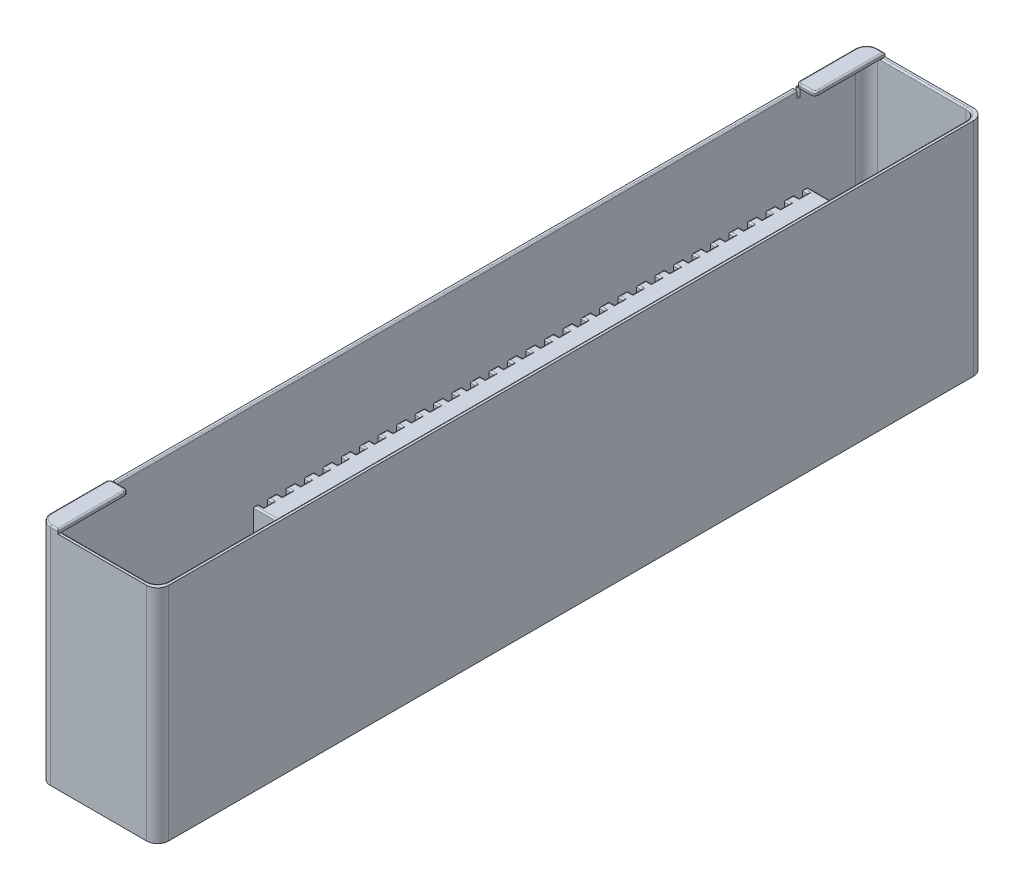
SolidWorks part; units mm, degrees
ref_plane "Front Plane" through (0, 0, 0) normal (0, 0, 1) x (1, 0, 0)
ref_plane "Top Plane" through (0, 0, 0) normal (0, 1, 0) x (1, 0, 0)
ref_plane "Right Plane" through (0, 0, 0) normal (1, 0, 0) x (0, 0, -1)
sketch "Sketch1" plane through (0, 0, 0) normal (0, 1, 0) x (1, 0, 0)
  line L0 (0, 0) -> (0, 2.2917) construction
  line L1 (-1.6, 11.2) -> (1.6, 11.2)
  line L2 (-1.6, 11.2) -> (-1.6, -11.2)
  line L3 (-1.6, -11.2) -> (1.6, -11.2)
  line L4 (1.6, 11.2) -> (1.6, -11.2)
  line L5 (0, 0) -> (0.8, 0) construction
  line L6 (-1.5, 11.1) -> (1.5, 11.1)
  line L7 (1.5, 11.1) -> (1.5, -11.1)
  line L8 (-1.5, -11.1) -> (1.5, -11.1)
  line L9 (-1.5, 11.1) -> (-1.5, -11.1)
  line L10 (-0.1, -0.1) -> (0.8, -0.1)
  line L11 (-0.1, -0.1) -> (-0.1, 2.2917)
  dimension "D1" = 3.2
  dimension "D2" = 22.4
  dimension "D3" = 0.1
extrude "Boss-Extrude1" add sketch "Sketch1" along normal blind 6 contours L4 L1 L2 L3 L9 L6 L7 L8
sketch "Sketch2" plane through (0, 0, 0) normal (0, -1, 0) x (1, 0, 0)
  line L1 (-1.6, 11.2) -> (1.6, 11.2)
  line L2 (-1.6, 11.2) -> (-1.6, -11.2)
  line L3 (-1.6, -11.2) -> (1.6, -11.2)
  line L4 (1.6, 11.2) -> (1.6, -11.2)
extrude "Boss-Extrude2" add sketch "Sketch2" against normal blind 0.1
sketch "Sketch3" plane through (0, 6, 0) normal (0, 1, 0) x (1, 0, 0)
  line L0 (-1.5, -11.1) -> (-1.5, -9.3) construction
  line L1 (-1.5, -11.1) -> (-1.5, 11.1) construction
  line L2 (-1.5, -9.3) -> (-1.2, -9.3)
  line L3 (-1.6, 11.2) -> (-1.6, -11.2) construction
  line L4 (-1.1, -9.4) -> (-1.1, -11.1)
  line L5 (-1.5, -11.1) -> (1.5, -11.1) construction
  line L6 (-1.1, -11.1) -> (-1.1, -11.2)
  line L7 (-1.6, -11.1) -> (-1.6, -9.4)
  line L8 (-1.6, -11.2) -> (1.6, -11.2) construction
  line L9 (-1.1, -11.2) -> (-1.6, -11.2)
  line L10 (-1.6, -11.2) -> (-1.6, -11.1)
  arc A0 (-1.5, -9.3) -> (-1.6, -9.4) centre (-1.5, -9.4) ccw
  arc A1 (-1.2, -9.3) -> (-1.1, -9.4) centre (-1.2, -9.4) cw
  point P15 (-1.6, -9.3)
  dimension "D3" = 0.1
  dimension "D1" = 1.8
  dimension "D2" = 0.5
extrude "Boss-Extrude4" add sketch "Sketch3" along normal blind 0.1
mirror "Mirror1" about plane through (0, 0, 0) normal (0, 0, 1) of "Boss-Extrude4"
sketch "Sketch4" plane through (0, 6, 0) normal (0, 1, 0) x (1, 0, 0)
  line L0 (-1.5, 9.3) -> (-1.2, 9.3)
  line L1 (-1.2, 9.3) -> (-1.2, 9.2142)
  line L2 (-1.2, 9.2142) -> (-1.7728, 9.2142)
  line L3 (-1.7728, 9.2142) -> (-1.7728, 9.3)
  line L4 (-1.7728, 9.3) -> (-1.5, 9.3)
  line L5 (0, 0) -> (-2.7647, 0) construction
  line L6 (-1.2, -9.3) -> (-1.2, -9.2142)
  line L7 (-1.7728, -9.2142) -> (-1.7728, -9.3)
  line L8 (-1.7728, -9.3) -> (-1.5, -9.3)
  line L9 (-1.5, -9.3) -> (-1.2, -9.3)
  line L10 (-1.2, -9.2142) -> (-1.7728, -9.2142)
extrude "Cut-Extrude1" cut sketch "Sketch4" against normal blind 0.2
sketch "Sketch5" plane through (0, 0.1, 0) normal (0, 1, 0) x (1, 0, 0)
  line L0 (0, 0) -> (1.3, 0) construction
  line L1 (1.3, 0) -> (1.3, 7.5)
  line L2 (1.3, 0) -> (1.3, -7.5)
  line L3 (1.5, 0) -> (1.3, 0) construction
  line L4 (1.5, 11.1) -> (1.5, -11.1) construction
  line L5 (1.3, 7.5) -> (0.5, 7.5)
  line L6 (0.5, 7.5) -> (0.5, -7.5)
  line L7 (0.5, -7.5) -> (1.3, -7.5)
  line L10 (0.5, 0.125) -> (0.5, -0.125)
  dimension "D1" = 0.2
  dimension "D2" = 7.5
  dimension "D3" = 7.5
  dimension "D4" = 0.8
extrude "Boss-Extrude5" add sketch "Sketch5" along normal blind 5.5 contours L6 L7 L2 L1 L5
sketch "Sketch6" plane through (0, 5.6, 0) normal (0, 1, 0) x (1, 0, 0)
  line L0 (0.5, 0) -> (0.7046, 0) construction
  line L1 (0.5, 7.5) -> (0.5, -7.5) construction
  line L2 (0.5, 0) -> (0.5, -0.125) construction
  line L3 (0.5, 7.5) -> (0.5, -7.5) construction
  line L4 (0.5, 0) -> (0.5, 0.125) construction
  line L5 (0.5, 0.125) -> (0.65, 0.125)
  line L6 (0.65, 0.125) -> (0.65, 0.375)
  line L7 (0.65, 0.375) -> (0.5, 0.375)
  line L8 (0.5, 0.375) -> (0.5, 0.125)
  line L9 (0.65, 0.875) -> (0.5, 0.875)
  line L10 (0.65, 0.625) -> (0.65, 0.875)
  line L11 (0.5, 0.625) -> (0.65, 0.625)
  line L12 (0.5, 0.875) -> (0.5, 0.625)
  line L13 (0.65, 1.375) -> (0.5, 1.375)
  line L14 (0.65, 1.125) -> (0.65, 1.375)
  line L15 (0.5, 1.125) -> (0.65, 1.125)
  line L16 (0.5, 1.375) -> (0.5, 1.125)
  line L17 (0.65, 1.875) -> (0.5, 1.875)
  line L18 (0.65, 1.625) -> (0.65, 1.875)
  line L19 (0.5, 1.625) -> (0.65, 1.625)
  line L20 (0.5, 1.875) -> (0.5, 1.625)
  line L21 (0.65, 2.375) -> (0.5, 2.375)
  line L22 (0.65, 2.125) -> (0.65, 2.375)
  line L23 (0.5, 2.125) -> (0.65, 2.125)
  line L24 (0.5, 2.375) -> (0.5, 2.125)
  line L25 (0.65, 2.875) -> (0.5, 2.875)
  line L26 (0.65, 2.625) -> (0.65, 2.875)
  line L27 (0.5, 2.625) -> (0.65, 2.625)
  line L28 (0.5, 2.875) -> (0.5, 2.625)
  line L29 (0.65, 3.375) -> (0.5, 3.375)
  line L30 (0.65, 3.125) -> (0.65, 3.375)
  line L31 (0.5, 3.125) -> (0.65, 3.125)
  line L32 (0.5, 3.375) -> (0.5, 3.125)
  line L33 (0.65, 3.875) -> (0.5, 3.875)
  line L34 (0.65, 3.625) -> (0.65, 3.875)
  line L35 (0.5, 3.625) -> (0.65, 3.625)
  line L36 (0.5, 3.875) -> (0.5, 3.625)
  line L37 (0.65, 4.375) -> (0.5, 4.375)
  line L38 (0.65, 4.125) -> (0.65, 4.375)
  line L39 (0.5, 4.125) -> (0.65, 4.125)
  line L40 (0.5, 4.375) -> (0.5, 4.125)
  line L41 (0.65, 4.875) -> (0.5, 4.875)
  line L42 (0.65, 4.625) -> (0.65, 4.875)
  line L43 (0.5, 4.625) -> (0.65, 4.625)
  line L44 (0.5, 4.875) -> (0.5, 4.625)
  line L45 (0.65, 5.375) -> (0.5, 5.375)
  line L46 (0.65, 5.125) -> (0.65, 5.375)
  line L47 (0.5, 5.125) -> (0.65, 5.125)
  line L48 (0.5, 5.375) -> (0.5, 5.125)
  line L49 (0.65, 5.875) -> (0.5, 5.875)
  line L50 (0.65, 5.625) -> (0.65, 5.875)
  line L51 (0.5, 5.625) -> (0.65, 5.625)
  line L52 (0.5, 5.875) -> (0.5, 5.625)
  line L53 (0.65, 6.375) -> (0.5, 6.375)
  line L54 (0.65, 6.125) -> (0.65, 6.375)
  line L55 (0.5, 6.125) -> (0.65, 6.125)
  line L56 (0.5, 6.375) -> (0.5, 6.125)
  line L57 (0.65, 6.875) -> (0.5, 6.875)
  line L58 (0.65, 6.625) -> (0.65, 6.875)
  line L59 (0.5, 6.625) -> (0.65, 6.625)
  line L60 (0.5, 6.875) -> (0.5, 6.625)
  line L61 (0.65, 7.375) -> (0.5, 7.375)
  line L62 (0.65, 7.125) -> (0.65, 7.375)
  line L63 (0.5, 7.125) -> (0.65, 7.125)
  line L64 (0.5, 7.375) -> (0.5, 7.125)
  line L65 (0.5, -7.375) -> (0.5, -7.125)
  line L66 (0.5, -7.125) -> (0.65, -7.125)
  line L67 (0.65, -7.125) -> (0.65, -7.375)
  line L68 (0.65, -7.375) -> (0.5, -7.375)
  line L69 (0.5, -6.875) -> (0.5, -6.625)
  line L70 (0.5, -6.625) -> (0.65, -6.625)
  line L71 (0.65, -6.625) -> (0.65, -6.875)
  line L72 (0.65, -6.875) -> (0.5, -6.875)
  line L73 (0.5, -6.375) -> (0.5, -6.125)
  line L74 (0.5, -6.125) -> (0.65, -6.125)
  line L75 (0.65, -6.125) -> (0.65, -6.375)
  line L76 (0.65, -6.375) -> (0.5, -6.375)
  line L77 (0.5, -5.875) -> (0.5, -5.625)
  line L78 (0.5, -5.625) -> (0.65, -5.625)
  line L79 (0.65, -5.625) -> (0.65, -5.875)
  line L80 (0.65, -5.875) -> (0.5, -5.875)
  line L81 (0.5, -5.375) -> (0.5, -5.125)
  line L82 (0.5, -5.125) -> (0.65, -5.125)
  line L83 (0.65, -5.125) -> (0.65, -5.375)
  line L84 (0.65, -5.375) -> (0.5, -5.375)
  line L85 (0.5, -4.875) -> (0.5, -4.625)
  line L86 (0.5, -4.625) -> (0.65, -4.625)
  line L87 (0.65, -4.625) -> (0.65, -4.875)
  line L88 (0.65, -4.875) -> (0.5, -4.875)
  line L89 (0.5, -4.375) -> (0.5, -4.125)
  line L90 (0.5, -4.125) -> (0.65, -4.125)
  line L91 (0.65, -4.125) -> (0.65, -4.375)
  line L92 (0.65, -4.375) -> (0.5, -4.375)
  line L93 (0.5, -3.875) -> (0.5, -3.625)
  line L94 (0.5, -3.625) -> (0.65, -3.625)
  line L95 (0.65, -3.625) -> (0.65, -3.875)
  line L96 (0.65, -3.875) -> (0.5, -3.875)
  line L97 (0.5, -3.375) -> (0.5, -3.125)
  line L98 (0.5, -3.125) -> (0.65, -3.125)
  line L99 (0.65, -3.125) -> (0.65, -3.375)
  line L100 (0.65, -3.375) -> (0.5, -3.375)
  line L101 (0.5, -2.875) -> (0.5, -2.625)
  line L102 (0.5, -2.625) -> (0.65, -2.625)
  line L103 (0.65, -2.625) -> (0.65, -2.875)
  line L104 (0.65, -2.875) -> (0.5, -2.875)
  line L105 (0.5, -2.375) -> (0.5, -2.125)
  line L106 (0.5, -2.125) -> (0.65, -2.125)
  line L107 (0.65, -2.125) -> (0.65, -2.375)
  line L108 (0.65, -2.375) -> (0.5, -2.375)
  line L109 (0.5, -1.875) -> (0.5, -1.625)
  line L110 (0.5, -1.625) -> (0.65, -1.625)
  line L111 (0.65, -1.625) -> (0.65, -1.875)
  line L112 (0.65, -1.875) -> (0.5, -1.875)
  line L113 (0.5, -1.375) -> (0.5, -1.125)
  line L114 (0.5, -1.125) -> (0.65, -1.125)
  line L115 (0.65, -1.125) -> (0.65, -1.375)
  line L116 (0.65, -1.375) -> (0.5, -1.375)
  line L117 (0.5, -0.875) -> (0.5, -0.625)
  line L118 (0.5, -0.625) -> (0.65, -0.625)
  line L119 (0.65, -0.625) -> (0.65, -0.875)
  line L120 (0.65, -0.875) -> (0.5, -0.875)
  line L121 (0.5, -0.375) -> (0.5, -0.125)
  line L122 (0.65, -0.375) -> (0.5, -0.375)
  line L123 (0.65, -0.125) -> (0.65, -0.375)
  line L124 (0.5, -0.125) -> (0.65, -0.125)
  dimension "D1" = 0.125
  dimension "D2" = 0.25
  dimension "D3" = 0.15
  dimension "D4" = 15
extrude "Cut-Extrude2" cut sketch "Sketch6" against normal blind 5.5
sketch "Sketch7" plane through (0, 0.1, 0) normal (0, 1, 0) x (1, 0, 0)
  line L0 (0.575, -7.125) -> (0.575, -7.375) construction
  line L1 (0.525, -7.15) -> (0.625, -7.15)
  line L2 (0.525, -7.15) -> (0.525, -7.35)
  line L3 (0.525, -7.35) -> (0.625, -7.35)
  line L4 (0.625, -7.15) -> (0.625, -7.35)
  line L5 (0.65, -7.125) -> (0.5, -7.125) construction
  line L6 (0.5, -7.375) -> (0.65, -7.375) construction
  line L7 (0.65, -7.25) -> (0.575, -7.25) construction
  line L8 (0.65, -7.375) -> (0.65, -7.125) construction
  line L9 (0.525, -6.65) -> (0.625, -6.65)
  line L10 (0.525, -6.65) -> (0.525, -6.85)
  line L11 (0.525, -6.85) -> (0.625, -6.85)
  line L12 (0.625, -6.65) -> (0.625, -6.85)
  line L13 (0.525, -6.15) -> (0.625, -6.15)
  line L14 (0.525, -6.15) -> (0.525, -6.35)
  line L15 (0.525, -6.35) -> (0.625, -6.35)
  line L16 (0.625, -6.15) -> (0.625, -6.35)
  line L17 (0.525, -5.65) -> (0.625, -5.65)
  line L18 (0.525, -5.65) -> (0.525, -5.85)
  line L19 (0.525, -5.85) -> (0.625, -5.85)
  line L20 (0.625, -5.65) -> (0.625, -5.85)
  line L21 (0.525, -5.15) -> (0.625, -5.15)
  line L22 (0.525, -5.15) -> (0.525, -5.35)
  line L23 (0.525, -5.35) -> (0.625, -5.35)
  line L24 (0.625, -5.15) -> (0.625, -5.35)
  line L25 (0.525, -4.65) -> (0.625, -4.65)
  line L26 (0.525, -4.65) -> (0.525, -4.85)
  line L27 (0.525, -4.85) -> (0.625, -4.85)
  line L28 (0.625, -4.65) -> (0.625, -4.85)
  line L29 (0.525, -4.15) -> (0.625, -4.15)
  line L30 (0.525, -4.15) -> (0.525, -4.35)
  line L31 (0.525, -4.35) -> (0.625, -4.35)
  line L32 (0.625, -4.15) -> (0.625, -4.35)
  line L33 (0.525, -3.65) -> (0.625, -3.65)
  line L34 (0.525, -3.65) -> (0.525, -3.85)
  line L35 (0.525, -3.85) -> (0.625, -3.85)
  line L36 (0.625, -3.65) -> (0.625, -3.85)
  line L37 (0.525, -3.15) -> (0.625, -3.15)
  line L38 (0.525, -3.15) -> (0.525, -3.35)
  line L39 (0.525, -3.35) -> (0.625, -3.35)
  line L40 (0.625, -3.15) -> (0.625, -3.35)
  line L41 (0.525, -2.65) -> (0.625, -2.65)
  line L42 (0.525, -2.65) -> (0.525, -2.85)
  line L43 (0.525, -2.85) -> (0.625, -2.85)
  line L44 (0.625, -2.65) -> (0.625, -2.85)
  line L45 (0.525, -2.15) -> (0.625, -2.15)
  line L46 (0.525, -2.15) -> (0.525, -2.35)
  line L47 (0.525, -2.35) -> (0.625, -2.35)
  line L48 (0.625, -2.15) -> (0.625, -2.35)
  line L49 (0.525, -1.65) -> (0.625, -1.65)
  line L50 (0.525, -1.65) -> (0.525, -1.85)
  line L51 (0.525, -1.85) -> (0.625, -1.85)
  line L52 (0.625, -1.65) -> (0.625, -1.85)
  line L53 (0.525, -1.15) -> (0.625, -1.15)
  line L54 (0.525, -1.15) -> (0.525, -1.35)
  line L55 (0.525, -1.35) -> (0.625, -1.35)
  line L56 (0.625, -1.15) -> (0.625, -1.35)
  line L57 (0.525, -0.65) -> (0.625, -0.65)
  line L58 (0.525, -0.65) -> (0.525, -0.85)
  line L59 (0.525, -0.85) -> (0.625, -0.85)
  line L60 (0.625, -0.65) -> (0.625, -0.85)
  line L61 (0.525, -0.15) -> (0.625, -0.15)
  line L62 (0.525, -0.15) -> (0.525, -0.35)
  line L63 (0.525, -0.35) -> (0.625, -0.35)
  line L64 (0.625, -0.15) -> (0.625, -0.35)
  line L65 (0.525, 0.35) -> (0.625, 0.35)
  line L66 (0.525, 0.35) -> (0.525, 0.15)
  line L67 (0.525, 0.15) -> (0.625, 0.15)
  line L68 (0.625, 0.35) -> (0.625, 0.15)
  line L69 (0.525, 0.85) -> (0.625, 0.85)
  line L70 (0.525, 0.85) -> (0.525, 0.65)
  line L71 (0.525, 0.65) -> (0.625, 0.65)
  line L72 (0.625, 0.85) -> (0.625, 0.65)
  line L73 (0.525, 1.35) -> (0.625, 1.35)
  line L74 (0.525, 1.35) -> (0.525, 1.15)
  line L75 (0.525, 1.15) -> (0.625, 1.15)
  line L76 (0.625, 1.35) -> (0.625, 1.15)
  line L77 (0.525, 1.85) -> (0.625, 1.85)
  line L78 (0.525, 1.85) -> (0.525, 1.65)
  line L79 (0.525, 1.65) -> (0.625, 1.65)
  line L80 (0.625, 1.85) -> (0.625, 1.65)
  line L81 (0.525, 2.35) -> (0.625, 2.35)
  line L82 (0.525, 2.35) -> (0.525, 2.15)
  line L83 (0.525, 2.15) -> (0.625, 2.15)
  line L84 (0.625, 2.35) -> (0.625, 2.15)
  line L85 (0.525, 2.85) -> (0.625, 2.85)
  line L86 (0.525, 2.85) -> (0.525, 2.65)
  line L87 (0.525, 2.65) -> (0.625, 2.65)
  line L88 (0.625, 2.85) -> (0.625, 2.65)
  line L89 (0.525, 3.35) -> (0.625, 3.35)
  line L90 (0.525, 3.35) -> (0.525, 3.15)
  line L91 (0.525, 3.15) -> (0.625, 3.15)
  line L92 (0.625, 3.35) -> (0.625, 3.15)
  line L93 (0.525, 3.85) -> (0.625, 3.85)
  line L94 (0.525, 3.85) -> (0.525, 3.65)
  line L95 (0.525, 3.65) -> (0.625, 3.65)
  line L96 (0.625, 3.85) -> (0.625, 3.65)
  line L97 (0.525, 4.35) -> (0.625, 4.35)
  line L98 (0.525, 4.35) -> (0.525, 4.15)
  line L99 (0.525, 4.15) -> (0.625, 4.15)
  line L100 (0.625, 4.35) -> (0.625, 4.15)
  line L101 (0.525, 4.85) -> (0.625, 4.85)
  line L102 (0.525, 4.85) -> (0.525, 4.65)
  line L103 (0.525, 4.65) -> (0.625, 4.65)
  line L104 (0.625, 4.85) -> (0.625, 4.65)
  line L105 (0.525, 5.35) -> (0.625, 5.35)
  line L106 (0.525, 5.35) -> (0.525, 5.15)
  line L107 (0.525, 5.15) -> (0.625, 5.15)
  line L108 (0.625, 5.35) -> (0.625, 5.15)
  line L109 (0.525, 5.85) -> (0.625, 5.85)
  line L110 (0.525, 5.85) -> (0.525, 5.65)
  line L111 (0.525, 5.65) -> (0.625, 5.65)
  line L112 (0.625, 5.85) -> (0.625, 5.65)
  line L113 (0.525, 6.35) -> (0.625, 6.35)
  line L114 (0.525, 6.35) -> (0.525, 6.15)
  line L115 (0.525, 6.15) -> (0.625, 6.15)
  line L116 (0.625, 6.35) -> (0.625, 6.15)
  line L117 (0.525, 6.85) -> (0.625, 6.85)
  line L118 (0.525, 6.85) -> (0.525, 6.65)
  line L119 (0.525, 6.65) -> (0.625, 6.65)
  line L120 (0.625, 6.85) -> (0.625, 6.65)
  line L121 (0.525, 7.35) -> (0.625, 7.35)
  line L122 (0.525, 7.35) -> (0.525, 7.15)
  line L123 (0.525, 7.15) -> (0.625, 7.15)
  line L124 (0.625, 7.35) -> (0.625, 7.15)
  dimension "D1" = 0.1
  dimension "D2" = 0.2
  dimension "D3" = 30
extrude "Boss-Extrude6" add sketch "Sketch7" along normal blind 5.3
fillet "Fillet1" radius 0.3 8 edges at (-1.5, 3.05, 11.1) (1.5, 3.05, 11.1) (-1.5, 3.05, -11.1) (1.5, 3.05, -11.1) (1.6, 3, -11.2) (-1.6, 3.05, -11.2) (1.6, 3, 11.2) (-1.6, 3.05, 11.2)
fillet "Fillet2" radius 0.041 94 edges at (0.65, 5.6, 4.75) (0.575, 5.6, 4.625) (0.5, 5.6, 0.5) (0.575, 5.6, 4.375) (0.65, 5.6, 4.25) (0.575, 5.6, 4.125) (0.575, 5.6, 3.875) (0.65, 5.6, 3.75) (0.575, 5.6, 3.625) (0.575, 5.6, 3.375) (0.65, 5.6, 3.25) (0.575, 5.6, 3.125) (0.575, 5.6, 2.875) (0.65, 5.6, 2.75) (0.575, 5.6, 2.625) (0.575, 5.6, 2.375) (0.65, 5.6, 2.25) (0.575, 5.6, 2.125) (0.575, 5.6, 1.875) (0.65, 5.6, 1.75) (0.575, 5.6, 1.625) (0.575, 5.6, 1.375) (0.65, 5.6, 1.25) (0.575, 5.6, 1.125) (0.575, 5.6, 0.875) (0.65, 5.6, 0.75) (0.575, 5.6, 0.625) (0.575, 5.6, 0.375) (0.65, 5.6, 0.25) (0.575, 5.6, 0.125) (0.575, 5.6, -0.125) (0.65, 5.6, -0.25) (0.575, 5.6, -0.375) (0.575, 5.6, -0.625) (0.65, 5.6, -0.75) (0.575, 5.6, -0.875) (0.575, 5.6, -1.125) (0.65, 5.6, -1.25) (0.575, 5.6, -1.375) (0.575, 5.6, -1.625) (0.65, 5.6, -1.75) (0.575, 5.6, -1.875) (0.575, 5.6, -2.125) (0.65, 5.6, -2.25) (0.575, 5.6, -2.375) (0.575, 5.6, -2.625) (0.65, 5.6, -2.75) (0.575, 5.6, -2.875) (0.575, 5.6, -3.125) (0.65, 5.6, -3.25) (0.575, 5.6, -3.375) (0.575, 5.6, -3.625) (0.65, 5.6, -3.75) (0.575, 5.6, -3.875) (0.575, 5.6, -4.125) (0.65, 5.6, -4.25) (0.575, 5.6, -4.375) (0.575, 5.6, -4.625) (0.65, 5.6, -4.75) (0.575, 5.6, -4.875) (0.575, 5.6, -5.125) (0.65, 5.6, -5.25) (0.575, 5.6, -5.375) (0.575, 5.6, -5.625) (0.65, 5.6, -5.75) (0.575, 5.6, -5.875) (0.575, 5.6, -6.125) (0.65, 5.6, -6.25) (0.575, 5.6, -6.375) (0.575, 5.6, -6.625) (0.65, 5.6, -6.75) (0.575, 5.6, -6.875) (0.575, 5.6, -7.125) (0.65, 5.6, -7.25) (0.575, 5.6, -7.375) (0.9, 5.6, -7.5) (1.3, 5.6, 0) (0.9, 5.6, 7.5) (0.575, 5.6, 7.375) (0.65, 5.6, 7.25) (0.575, 5.6, 7.125) (0.575, 5.6, 6.875) (0.65, 5.6, 6.75) (0.575, 5.6, 6.625) (0.575, 5.6, 6.375) (0.65, 5.6, 6.25) (0.575, 5.6, 6.125) (0.575, 5.6, 5.875) (0.65, 5.6, 5.75) (0.575, 5.6, 5.625) (0.575, 5.6, 5.375) (0.65, 5.6, 5.25) (0.575, 5.6, 5.125) (0.575, 5.6, 4.875)
fillet "Fillet3" radius 0.041 20 edges at (-1.1, 6.1, 10.3) (-1.1293, 6.1, 9.3293) (-1.2, 6.1, 11.2) (-1.5121, 6.1, 11.1121) (-1.6, 6.1, 10.15) (-1.5707, 6.1, 9.3293) (-1.2, 6.1, -11.2) (-1.5121, 6.1, -11.1121) (-1.6, 6.1, -10.15) (-1.5707, 6.1, -9.3293) (-1.35, 6.1, -9.3) (-1.1293, 6.1, -9.3293) (0.05, 6, -11.1) (1.4121, 6, -11.0121) (0.05, 6, 11.1) (1.4121, 6, 11.0121) (-1.35, 6.1, 9.3) (-1.5, 6, 0) (-1.1, 6.1, -10.3) (1.5, 6, 0)
sketch "Sketch8" plane through (0, 0.1, 0) normal (0, 1, 0) x (1, 0, 0)
  line L0 (0, 0) -> (-1.5, 0) construction
  line L1 (-1.5, -10.8) -> (-1.5, 10.8) construction
  line L2 (1.5, -10.8) -> (1.5, 10.8) construction
  line L3 (1.5, 8.4) -> (1.15, 8.4)
  line L4 (1.5, 8.4) -> (1.5, 8.3)
  line L5 (1.5, 8.3) -> (1.15, 8.3)
  line L6 (1.15, 8.4) -> (1.15, 8.3)
  line L7 (1.3, 7.5) -> (1.5, 7.5) construction
  line L8 (1.5, 7.5) -> (1.5, 8.3) construction
  line L9 (1.15, -8.4) -> (1.15, -8.3)
  line L10 (1.5, -8.4) -> (1.15, -8.4)
  line L11 (1.5, -8.4) -> (1.5, -8.3)
  line L12 (1.5, -8.3) -> (1.15, -8.3)
  dimension "D1" = 0.8
  dimension "D2" = 0.1
  dimension "D3" = 0.35
extrude "Boss-Extrude7" add sketch "Sketch8" along normal blind 5.5
